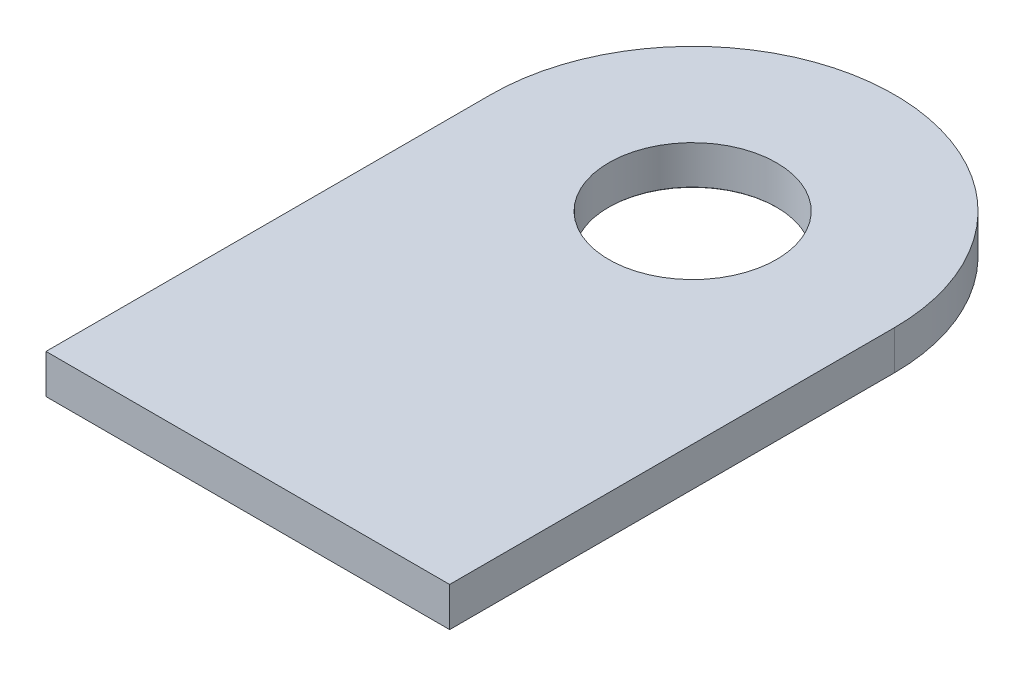
SolidWorks part; units mm, degrees
ref_plane "Front Plane" through (0, 0, 0) normal (0, 0, 1) x (1, 0, 0)
ref_plane "Top Plane" through (0, 0, 0) normal (0, 1, 0) x (1, 0, 0)
ref_plane "Right Plane" through (0, 0, 0) normal (1, 0, 0) x (0, 0, -1)
sketch "Sketch1" plane through (0, 0, 0) normal (0, 1, 0) x (1, 0, 0)
  line L0 (-7.94, 0) -> (-7.94, -17.5)
  line L1 (-7.94, -17.5) -> (7.94, -17.5)
  line L2 (7.94, -17.5) -> (7.94, 0)
  circle A0 centre (0, 0) radius 7.94
  dimension "D1" = 15.88
  dimension "D2" = 17.5
extrude "Boss-Extrude1" add sketch "Sketch1" along normal blind 1.54 contours A0 | A0 L0 L1 L2 region at (0, 0, 11.7286) region at (0, 0, 0)
hole_wizard "M6 Clearance Hole1" positions "Sketch4" profile "Sketch3" hole size "M6" standard "ANSI Metric" end condition through all
sketch "Sketch4" plane through (0, 0, 0) normal (0, -1, 0) x (-1, 0, 0)
  point P0 (0, 0)
sketch "Sketch3" plane through (0, 0, 0) normal (1, 0, 0) x (0, 0, -1)
  line L0 (0, 0) -> (0, 1.54)
  line L1 (0, 1.54) -> (3.3, 1.54)
  line L2 (3.3, 1.54) -> (3.3, 0.025)
  line L3 (3.3, 0.025) -> (3.325, 0)
  line L5 (3.325, 0) -> (0, 0)
  line L6 (-3.3, 0.025) -> (-3.325, 0) construction
  line L11 (0, -6.35) -> (0, 107.95) construction
  dimension "Thru Hole Dia." = 6.6
  dimension "Thru Hole Depth" = 1.54
  dimension "Near C'Sink Dia." = 6.65
  dimension "Near C'Sink Angle" = 90
